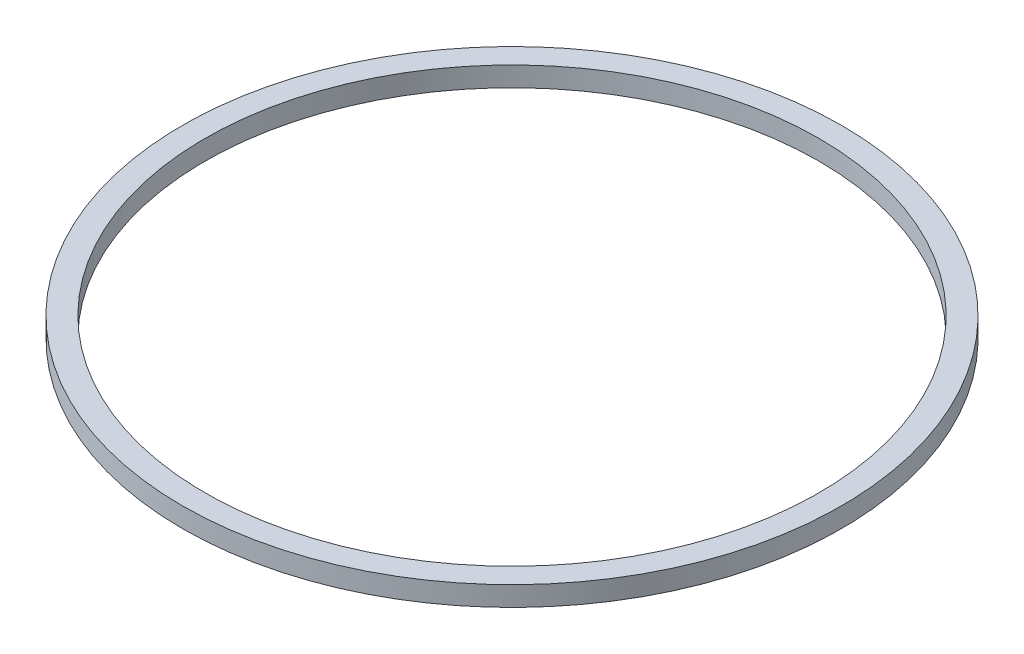
SolidWorks part; units mm, degrees
material "Hexcel AS4C (3000 Filaments)"
ref_plane "Front Plane" through (0, 0, 0) normal (0, 0, 1) x (1, 0, 0)
ref_plane "Top Plane" through (0, 0, 0) normal (0, 1, 0) x (1, 0, 0)
ref_plane "Right Plane" through (0, 0, 0) normal (1, 0, 0) x (0, 0, -1)
sketch "Sketch1" plane through (0, 0, 0) normal (0, 0, 1) x (1, 0, 0)
  line L0 (-102, 3.175) -> (-102, 9.735) construction
  line L1 (-109.5, 3.175) -> (-109.5, 9.735) construction
  line L2 (-102, 3.175) -> (-102, 9.735)
  line L3 (-109.5, 3.175) -> (-109.5, 9.735)
  line L4 (-109.5, 9.735) -> (-102, 9.735)
  line L5 (-102, 3.175) -> (-109.5, 3.175)
  line L6 (0, -200069.0475) -> (0, 200086.9028) construction
  line L7 (0, -200069.0475) -> (0, 200086.9028) construction
revolve "Revolve1" add sketch "Sketch1" angle 360 about L7
